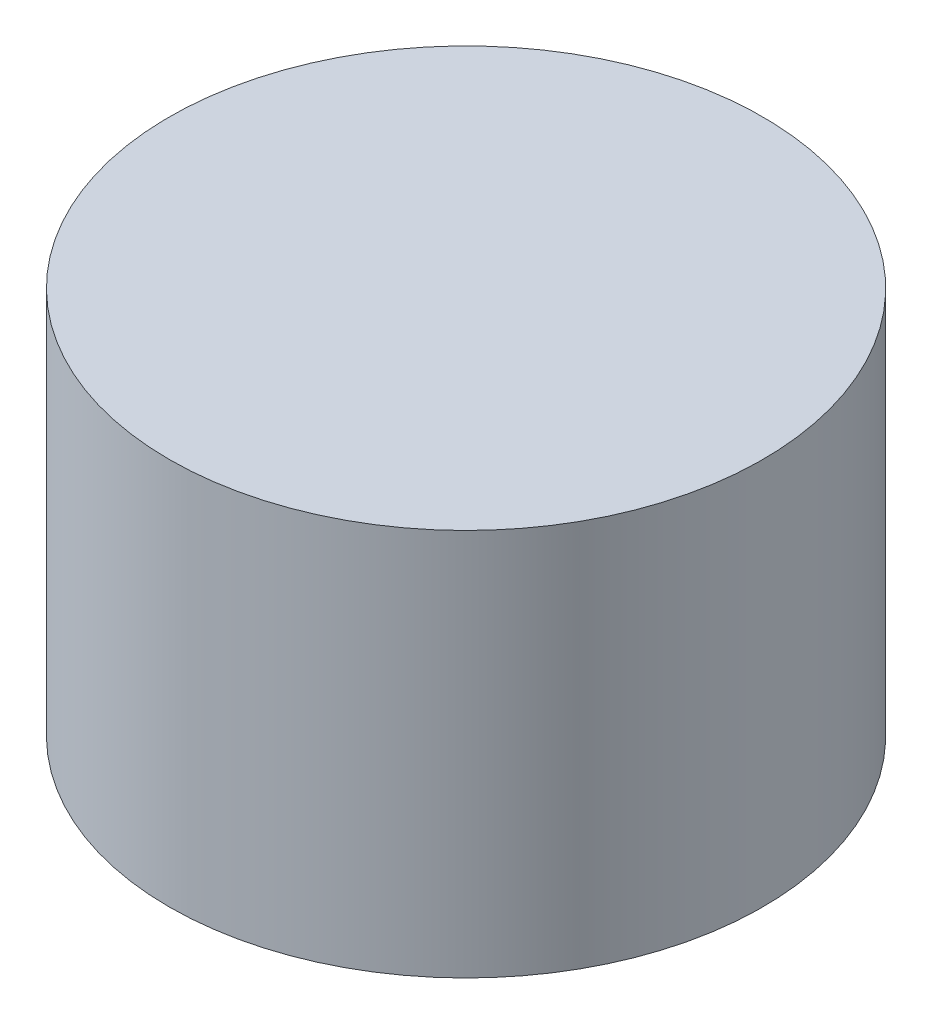
SolidWorks part; units mm, degrees
material "6061 합금"
ref_plane "정면" through (0, 0, 0) normal (0, 0, 1) x (1, 0, 0)
ref_plane "윗면" through (0, 0, 0) normal (0, 1, 0) x (1, 0, 0)
ref_plane "우측면" through (0, 0, 0) normal (1, 0, 0) x (0, 0, -1)
sketch "스케치1" plane through (0, 0, 0) normal (0, 1, 0) x (1, 0, 0)
  circle A0 centre (0, 0) radius 49
  circle A1 centre (0, 0) radius 35
  dimension "D1" = 98
  dimension "D2" = 70
extrude "보스-돌출1" add sketch "스케치1" along normal blind 64 contours A0
extrude "컷-돌출1" cut sketch "스케치1<3>" along normal blind 31 from offset 16.5 contours A1 region at (0, 0, 0)
sketch "스케치1<3>" plane through (0, 0, 0) normal (0, 1, 0) x (1, 0, 0) same geometry as "스케치1"
sketch "스케치2" plane through (0, 0, 0) normal (0, 0, 1) x (1, 0, 0)
  line L0 (0, 64) -> (0, 0) construction
  line L1 (49, 64) -> (-49, 64) construction
  line L2 (0, 0) -> (0, -59) construction
  dimension "D1" = 59
